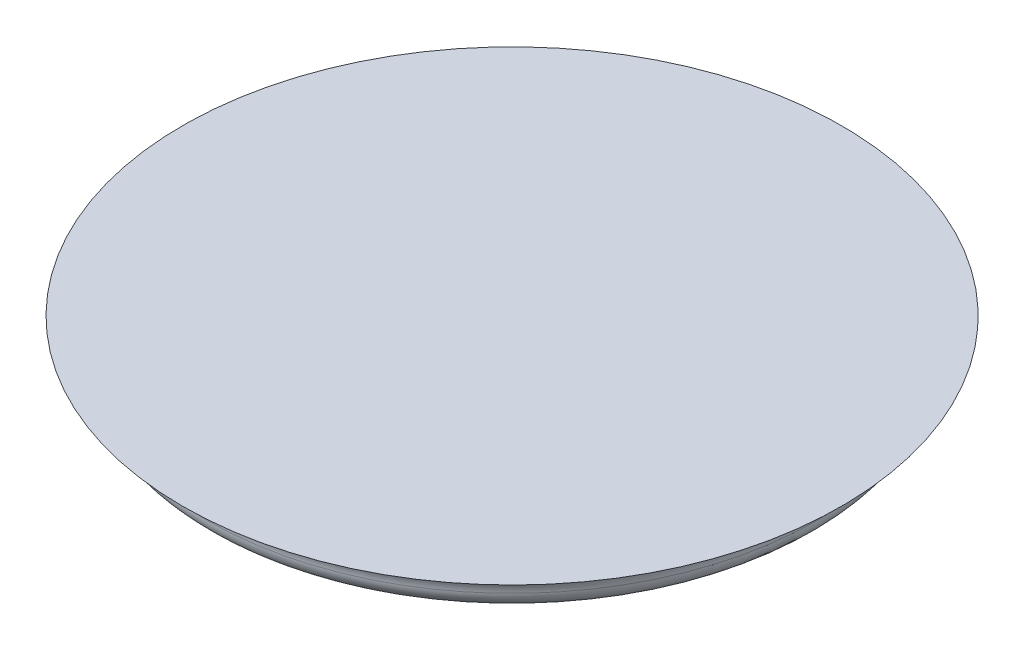
SolidWorks part; units mm, degrees
ref_plane "Front Plane" through (0, 0, 0) normal (0, 0, 1) x (1, 0, 0)
ref_plane "Top Plane" through (0, 0, 0) normal (0, 1, 0) x (1, 0, 0)
ref_plane "Right Plane" through (0, 0, 0) normal (1, 0, 0) x (0, 0, -1)
sketch "Sketch1" plane through (0, 0, 0) normal (0, 0, 1) x (1, 0, 0)
  line L1 (-100, 2) -> (100, 2)
  line L2 (-100, 2) -> (-100, 0)
  line L3 (-100, 0) -> (100, 0)
  line L4 (100, 2) -> (100, 0)
  dimension "D1" = 200
  dimension "D2" = 2
extrude "Boss-Extrude1" add sketch "Sketch1" along normal mid plane 120
sketch "Sketch2" plane through (0, 0, 0) normal (0, -1, 0) x (1, 0, 0)
  circle A0 centre (0, 0) radius 37
  dimension "D1" = 74
extrude "Boss-Extrude2" add sketch "Sketch2" along normal blind 5
fillet "Fillet1" radius 2 1 edges at (0, -5, -37)
fillet "Fillet2" radius 3 1 edges at (0, 0, -37)
sketch "Sketch4" plane through (-100, 0, 0) normal (-1, 0, 0) x (0, 0, 1)
  line L4 (-60, 2) -> (-60, 0)
  line L5 (-60, 0) -> (60, 0)
  line L6 (60, 0) -> (60, 2)
  line L7 (60, 2) -> (-60, 2)
  line L8 (-60, 2) -> (-60, 0)
  line L9 (-60, 0) -> (60, 0)
  line L10 (60, 0) -> (60, 2)
  line L11 (60, 2) -> (-60, 2)
  dimension "D1" = 0
extrude "Cut-Extrude1" cut sketch "Sketch4" against normal through all
sketch "Orientation Sketch" plane through (0, 0, 0) normal (0, 1, 0) x (1, 0, 0)
  circle A0 centre (0, 0) radius 40 construction
  circle A1 centre (0, 0) radius 40
  point P3 (0, 0)
other "FormTool1"
